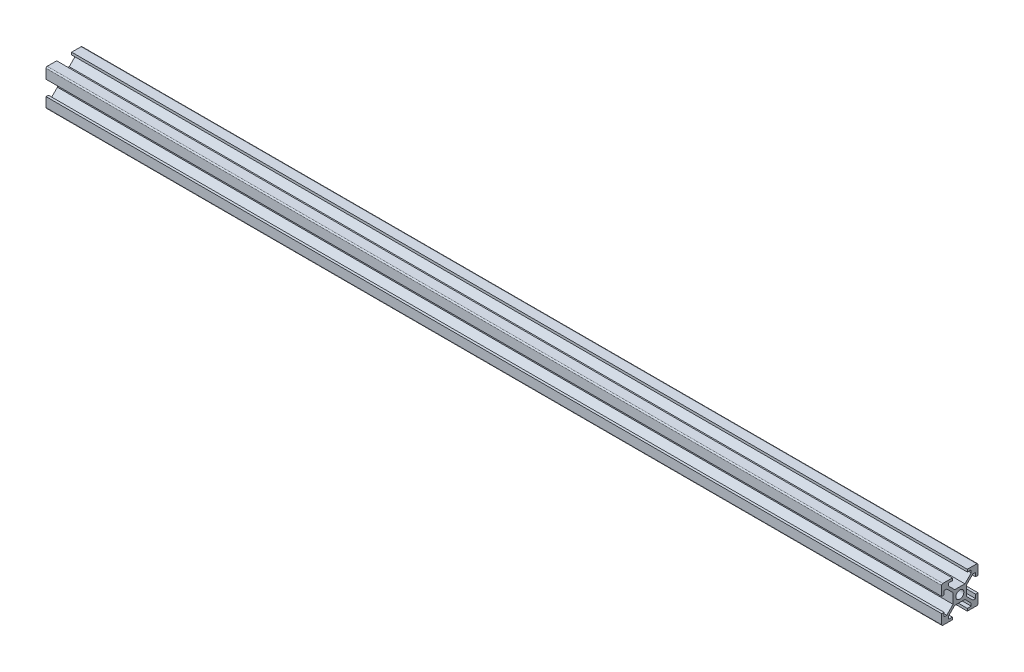
SolidWorks part; units mm, degrees
ref_plane "前视基准面" through (0, 0, 0) normal (0, 0, 1) x (1, 0, 0)
ref_plane "上视基准面" through (0, 0, 0) normal (0, 1, 0) x (1, 0, 0)
ref_plane "右视基准面" through (0, 0, 0) normal (1, 0, 0) x (0, 0, -1)
sketch "草图2" plane through (0, 0, 0) normal (1, 0, 0) x (0, 0, -1)
  line L0 (-3.1, 7.5) -> (3.1, 7.5)
  line L1 (-7, 7.5) -> (7, 7.5)
  line L2 (-7.5, 7) -> (-7.5, -7)
  line L3 (-7, -7.5) -> (7, -7.5)
  line L4 (7.5, 7) -> (7.5, -7)
  line L5 (-3.1, 7.5) -> (-3.1, 6.5)
  line L6 (-3.1, 6.5) -> (-4.7, 6.5)
  line L7 (-4.7, 6.5) -> (-4.7, 5.4071)
  line L8 (-4.7, 5.4071) -> (-2.0929, 2.8)
  line L9 (-2.0929, 2.8) -> (2.0929, 2.8)
  line L10 (2.0929, 2.8) -> (4.7, 5.4071)
  line L11 (4.7, 5.4071) -> (4.7, 6.5)
  line L12 (4.7, 6.5) -> (3.1, 6.5)
  line L13 (3.1, 6.5) -> (3.1, 7.5)
  line L14 (-7.5, -7.5) -> (7.5, 7.5) construction
  line L15 (7.5, -7.5) -> (-7.5, 7.5) construction
  line L17 (-2.8, 2.8) -> (2.8, 2.8)
  line L18 (-2.8, 2.8) -> (-2.8, -2.8)
  line L19 (-2.8, -2.8) -> (2.8, -2.8)
  line L20 (2.8, 2.8) -> (2.8, -2.8)
  line L21 (-2.8, 2.8) -> (2.8, -2.8) construction
  line L22 (-2.8, -2.8) -> (2.8, 2.8) construction
  line L52 (7.5, 3.1) -> (7.5, -3.1)
  line L53 (6.5, -3.1) -> (7.5, -3.1)
  line L54 (6.5, -4.7) -> (6.5, -3.1)
  line L55 (5.4071, -4.7) -> (6.5, -4.7)
  line L56 (2.8, -2.0929) -> (5.4071, -4.7)
  line L57 (2.8, 2.0929) -> (2.8, -2.0929)
  line L58 (5.4071, 4.7) -> (2.8, 2.0929)
  line L59 (6.5, 4.7) -> (5.4071, 4.7)
  line L60 (6.5, 3.1) -> (6.5, 4.7)
  line L61 (7.5, 3.1) -> (6.5, 3.1)
  line L62 (3.1, -7.5) -> (-3.1, -7.5)
  line L63 (-3.1, -6.5) -> (-3.1, -7.5)
  line L64 (-4.7, -6.5) -> (-3.1, -6.5)
  line L65 (-4.7, -5.4071) -> (-4.7, -6.5)
  line L66 (-2.0929, -2.8) -> (-4.7, -5.4071)
  line L67 (2.0929, -2.8) -> (-2.0929, -2.8)
  line L68 (4.7, -5.4071) -> (2.0929, -2.8)
  line L69 (4.7, -6.5) -> (4.7, -5.4071)
  line L70 (3.1, -6.5) -> (4.7, -6.5)
  line L71 (3.1, -7.5) -> (3.1, -6.5)
  line L72 (-7.5, -3.1) -> (-7.5, 3.1)
  line L73 (-6.5, 3.1) -> (-7.5, 3.1)
  line L74 (-6.5, 4.7) -> (-6.5, 3.1)
  line L75 (-5.4071, 4.7) -> (-6.5, 4.7)
  line L76 (-2.8, 2.0929) -> (-5.4071, 4.7)
  line L77 (-2.8, -2.0929) -> (-2.8, 2.0929)
  line L78 (-5.4071, -4.7) -> (-2.8, -2.0929)
  line L79 (-6.5, -4.7) -> (-5.4071, -4.7)
  line L80 (-6.5, -3.1) -> (-6.5, -4.7)
  line L81 (-7.5, -3.1) -> (-6.5, -3.1)
  line L82 (0, 0) -> (2.0929, 2.8) construction
  line L83 (0, 0) -> (2.8, -2.0929) construction
  circle A0 centre (0, 0) radius 1.65
  circle A1 centre (-7, 7) radius 0.5 construction
  circle A2 centre (-7, -7) radius 0.5 construction
  circle A3 centre (7, -7) radius 0.5 construction
  circle A4 centre (7, 7) radius 0.5 construction
  arc A5 (7, 7.5) -> (7.5, 7) centre (7, 7) cw
  arc A6 (7, -7.5) -> (7.5, -7) centre (7, -7) ccw
  arc A7 (-7.5, -7) -> (-7, -7.5) centre (-7, -7) ccw
  arc A8 (-7, 7.5) -> (-7.5, 7) centre (-7, 7) ccw
  point P16 (0, 0)
  point P28 (0, 0)
  point P50 (0, 7.5)
  point P52 (7.5, 0)
  point P62 (-7, -7)
  point P65 (7, -7)
  point P68 (7, 7)
  dimension "D3" = 3.3
  dimension "D12" = 1
  dimension "D13" = 1
  dimension "D14" = 1
  dimension "D15" = 1
  dimension "D16" = 0.5
  dimension "D1" = 15
  dimension "D2" = 6.2
  dimension "D4" = 5.6
  dimension "D5" = 9.4
  dimension "D6" = 0.5
  dimension "D7" = 0.5
  dimension "D8" = 4.7
  dimension "D9" = 1
  dimension "D10" = 4
  dimension "D11" = 90
extrude "凸台-拉伸1" add sketch "草图2" along normal blind 370 contours L2 A7 L3 A6 L4 A5 L1 A8
extrude "切除-拉伸2" cut sketch "草图2<4>" against normal through all and the other way through all contours L3 L71 L70 L69 L68 L19 L66 L65 L64 L63 | L2 L81 L80 L79 L78 L18 L76 L75 L74 L73 | L12 L13 L0 L5 L6 L7 L8 L9 L10 L11 | L4 L61 L60 L59 L58 L20 L56 L55 L54 L53 | A0 region at (0, 5.2713, 0) region at (0, 0, 5.2713) region at (0, 0, -5.2713) region at (0, -5.2713, 0) region at (0, 0, 0)
sketch "草图2<4>" plane through (0, 0, 0) normal (1, 0, 0) x (0, 0, -1) same geometry as "草图2"
